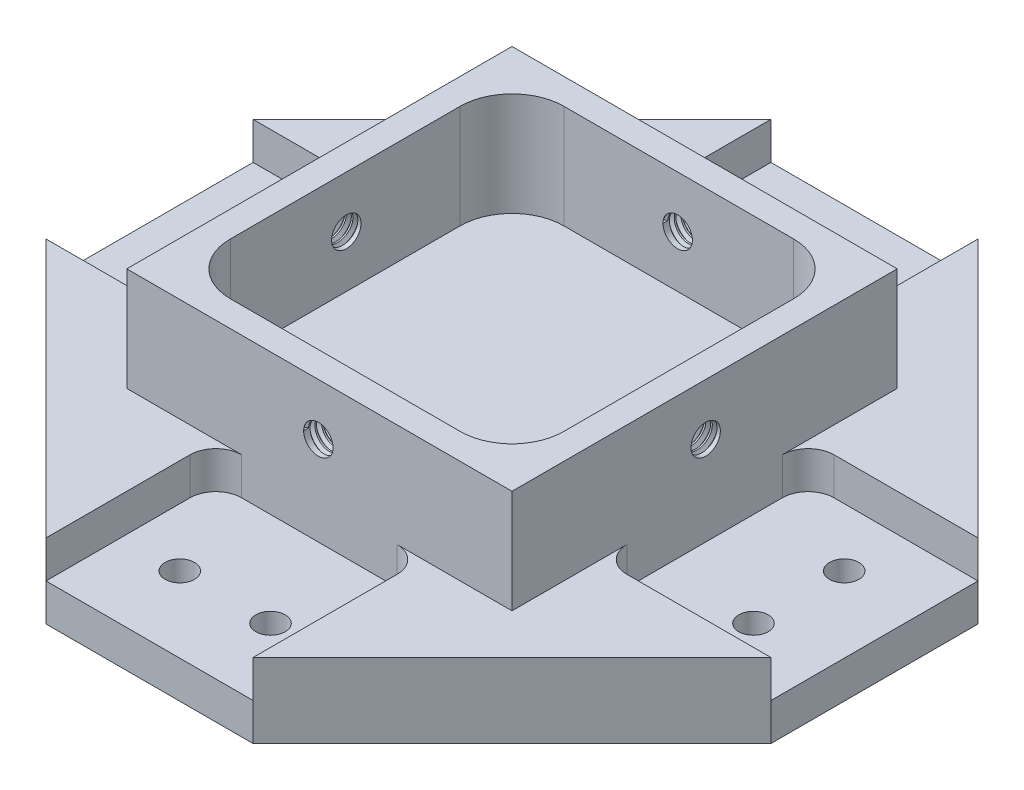
SolidWorks part; units mm, degrees
material "6061 Alloy"
ref_plane "Front Plane" through (0, 0, 0) normal (0, 0, 1) x (1, 0, 0)
ref_plane "Top Plane" through (0, 0, 0) normal (0, 1, 0) x (1, 0, 0)
ref_plane "Right Plane" through (0, 0, 0) normal (1, 0, 0) x (0, 0, -1)
sketch "Sketch1" plane through (0, 0, 0) normal (0, 1, 0) x (1, 0, 0)
  line L1 (0, 0) -> (88.9, 0)
  line L2 (0, 0) -> (0, 88.9)
  line L3 (0, 88.9) -> (88.9, 88.9)
  line L4 (88.9, 0) -> (88.9, 88.9)
  dimension "D1" = 88.9
  dimension "D2" = 88.9
extrude "Boss-Extrude1" add sketch "Sketch1" along normal blind 9.144
sketch "Sketch2" plane through (0, 9.144, 0) normal (0, 1, 0) x (1, 0, 0)
  line L0 (88.9, 88.9) -> (0, 88.9) construction
  line L1 (31.75, 88.9) -> (57.15, 88.9)
  line L2 (31.75, 88.9) -> (31.75, 67.31)
  line L3 (31.75, 67.31) -> (57.15, 67.31)
  line L4 (57.15, 88.9) -> (57.15, 67.31)
  line L5 (0, 88.9) -> (0, 0) construction
  line L6 (0, 57.15) -> (21.59, 57.15)
  line L7 (0, 57.15) -> (0, 31.75)
  line L8 (0, 31.75) -> (21.59, 31.75)
  line L9 (21.59, 57.15) -> (21.59, 31.75)
  line L10 (0, 0) -> (88.9, 0) construction
  line L11 (31.75, 0) -> (57.15, 0)
  line L12 (31.75, 0) -> (31.75, 21.59)
  line L13 (31.75, 21.59) -> (57.15, 21.59)
  line L14 (57.15, 0) -> (57.15, 21.59)
  line L15 (88.9, 0) -> (88.9, 88.9) construction
  line L16 (88.9, 57.15) -> (67.31, 57.15)
  line L17 (88.9, 57.15) -> (88.9, 31.75)
  line L18 (88.9, 31.75) -> (67.31, 31.75)
  line L19 (67.31, 57.15) -> (67.31, 31.75)
  dimension "D1" = 31.75
  dimension "D2" = 25.4
  dimension "D3" = 25.4
  dimension "D4" = 31.75
  dimension "D5" = 25.4
  dimension "D6" = 31.75
  dimension "D7" = 25.4
  dimension "D8" = 31.75
  dimension "D9" = 21.59
  dimension "D10" = 21.59
  dimension "D11" = 21.59
  dimension "D12" = 21.59
extrude "Cut-Extrude1" cut sketch "Sketch2" against normal blind 4.572
sketch "Sketch3" plane through (0, 9.144, 0) normal (0, 1, 0) x (1, 0, 0)
  line L0 (31.75, 88.9) -> (0, 88.9) construction
  line L1 (20.6375, 68.2625) -> (68.2625, 68.2625)
  line L2 (20.6375, 68.2625) -> (20.6375, 20.6375)
  line L3 (20.6375, 20.6375) -> (68.2625, 20.6375)
  line L4 (68.2625, 68.2625) -> (68.2625, 20.6375)
  line L5 (0, 31.75) -> (0, 0) construction
  line L6 (88.9, 31.75) -> (88.9, 57.15) construction
  line L7 (57.15, 88.9) -> (31.75, 88.9) construction
  line L8 (0, 57.15) -> (0, 31.75) construction
  line L9 (31.75, 0) -> (57.15, 0) construction
  circle A0 centre (28.194, 44.45) radius 2.4
  circle A1 centre (44.45, 60.706) radius 2.4
  circle A2 centre (60.706, 44.45) radius 2.4
  circle A3 centre (44.45, 28.194) radius 2.4
  dimension "D5" = 4.8
  dimension "D6" = 4.8
  dimension "D7" = 4.8
  dimension "D8" = 4.8
  dimension "D1" = 47.625
  dimension "D2" = 47.625
  dimension "D3" = 20.6375
  dimension "D4" = 20.6375
  dimension "D9" = 28.194
  dimension "D10" = 28.194
  dimension "D11" = 28.194
  dimension "D12" = 28.194
  dimension "D13" = 23.8125
  dimension "D14" = 23.8125
  dimension "D15" = 23.8125
  dimension "D16" = 23.8125
extrude "Cut-Extrude2" [suppressed] cut sketch "Sketch3" against normal through all contours A2 | A1 | A0 | A3
sketch "Sketch4" plane through (0, 4.572, 0) normal (0, 1, 0) x (1, 0, 0)
  line L0 (0, 57.15) -> (0, 31.75) construction
  line L1 (57.15, 88.9) -> (31.75, 88.9) construction
  line L2 (88.9, 31.75) -> (88.9, 57.15) construction
  line L3 (31.75, 0) -> (57.15, 0) construction
  line L4 (0, 31.75) -> (21.59, 31.75) construction
  line L5 (31.75, 21.59) -> (31.75, 0) construction
  line L6 (67.31, 31.75) -> (88.9, 31.75) construction
  line L7 (57.15, 67.31) -> (57.15, 88.9) construction
  circle A0 centre (79.629, 50.0126) radius 1.8034
  circle A1 centre (79.629, 38.8874) radius 1.8034
  circle A2 centre (50.0126, 79.629) radius 1.8034
  circle A3 centre (38.8874, 79.629) radius 1.8034
  circle A4 centre (9.271, 50.0126) radius 1.8034
  circle A5 centre (9.271, 38.8874) radius 1.8034
  circle A6 centre (38.8874, 9.271) radius 1.8034
  circle A7 centre (50.0126, 9.271) radius 1.8034
  dimension "D1" = 3.6068
  dimension "D2" = 3.6068
  dimension "D3" = 3.6068
  dimension "D4" = 3.6068
  dimension "D5" = 3.6068
  dimension "D6" = 3.6068
  dimension "D7" = 3.6068
  dimension "D8" = 3.6068
  dimension "D9" = 9.271
  dimension "D10" = 9.271
  dimension "D11" = 9.271
  dimension "D12" = 9.271
  dimension "D13" = 9.271
  dimension "D14" = 9.271
  dimension ".313" = 9.271
  dimension "D16" = 9.271
  dimension "D17" = 11.1252
  dimension "D18" = 7.1374
  dimension "D19" = 7.1374
  dimension "D20" = 11.1252
  dimension "D21" = 7.1374
  dimension "D22" = 11.1252
  dimension "D23" = 7.1374
  dimension "D24" = 11.1252
extrude "Cut-Extrude3" cut sketch "Sketch4" against normal through all
sketch "Sketch5" plane through (0, 9.144, 0) normal (0, 1, 0) x (1, 0, 0)
  line L0 (88.9, 88.9) -> (57.15, 88.9) construction
  line L1 (88.9, 31.75) -> (88.9, 57.15) construction
  circle A0 centre (44.45, 44.45) radius 6.35
  dimension "D1" = 12.7
  dimension "D2" = 44.45
  dimension "D3" = 44.45
extrude "Cut-Extrude4" [suppressed] cut sketch "Sketch5" against normal through all
sketch "Sketch6" plane through (0, 9.144, 0) normal (0, 1, 0) x (1, 0, 0)
  line L0 (88.9, 31.75) -> (57.15, 0)
  line L1 (57.15, 0) -> (88.9, 0)
  line L2 (88.9, 0) -> (88.9, 31.75)
extrude "Cut-Extrude5" cut sketch "Sketch6" against normal through all
sketch "Sketch7" plane through (0, 9.144, 0) normal (0, 1, 0) x (1, 0, 0)
  line L0 (0, 88.9) -> (0, 57.15) construction
  line L1 (20.828, 68.072) -> (68.072, 68.072)
  line L2 (20.828, 68.072) -> (20.828, 20.828)
  line L3 (20.828, 20.828) -> (68.072, 20.828)
  line L4 (68.072, 68.072) -> (68.072, 20.828)
  line L5 (0, 0) -> (31.75, 0) construction
  line L7 (24.003, 24.003) -> (64.897, 24.003)
  line L8 (24.003, 24.003) -> (24.003, 64.897)
  line L9 (24.003, 64.897) -> (64.897, 64.897)
  line L10 (64.897, 24.003) -> (64.897, 64.897)
  dimension "D1" = 47.244
  dimension "D2" = 47.244
  dimension "D3" = 20.828
  dimension "D4" = 20.828
  dimension "D5" = 3.175
  dimension "D6" = 3.175
  dimension "D7" = 3.175
  dimension "D8" = 3.175
extrude "Boss-Extrude2" add sketch "Sketch7" along normal blind 12.7 and the other way up to next (4.572 mm away)
fillet "Fillet9" radius 6.35 1 edges at (64.897, 15.494, -24.003)
fillet "Fillet10" radius 6.35 1 edges at (24.003, 15.494, -24.003)
fillet "Fillet11" radius 6.35 1 edges at (64.897, 15.494, -64.897)
fillet "Fillet12" radius 6.35 1 edges at (24.003, 15.494, -64.897)
fillet "Fillet15" radius 3.175 1 edges at (20.828, 6.858, -57.15)
fillet "Fillet16" radius 3.175 1 edges at (31.75, 6.858, -20.828)
fillet "Fillet17" radius 3.175 1 edges at (57.15, 6.858, -20.828)
fillet "Fillet18" radius 3.175 1 edges at (68.072, 6.858, -57.15)
fillet "Fillet19" radius 3.175 1 edges at (68.072, 6.858, -31.75)
fillet "Fillet20" radius 3.175 1 edges at (31.75, 6.858, -68.072)
fillet "Fillet21" radius 3.175 1 edges at (57.15, 6.858, -68.072)
fillet "Fillet22" radius 3.175 1 edges at (20.828, 6.858, -31.75)
sketch "Sketch9" plane through (0, 0, -68.072) normal (0, 0, -1) x (-1, 0, 0)
  line L0 (-68.072, 21.844) -> (-68.072, 9.144) construction
  line L1 (-68.072, 21.844) -> (-20.828, 21.844) construction
  circle A0 centre (-44.323, 15.494) radius 1.8034
  dimension "D1" = 3.6068
  dimension "D2" = 23.749
  dimension "D3" = 6.35
extrude "Cut-Extrude6" cut sketch "Sketch9" against normal through all
sketch "Sketch10" plane through (68.072, 0, 0) normal (1, 0, 0) x (0, 0, -1)
  line L0 (20.828, 21.844) -> (68.072, 21.844) construction
  line L1 (20.828, 21.844) -> (20.828, 9.144) construction
  circle A0 centre (44.577, 15.494) radius 1.8034
  dimension "D1" = 3.6068
  dimension "D2" = 6.35
  dimension "D3" = 23.749
extrude "Cut-Extrude7" cut sketch "Sketch10" against normal through all
sketch "Sketch12" plane through (0, 9.144, 0) normal (0, 1, 0) x (1, 0, 0)
  line L0 (0, 31.75) -> (31.75, 0)
  line L1 (31.75, 0) -> (0, 0)
  line L2 (0, 0) -> (0, 31.75)
  line L3 (57.15, 88.9) -> (88.9, 57.15)
  line L4 (88.9, 57.15) -> (88.9, 88.9)
  line L5 (88.9, 88.9) -> (57.15, 88.9)
  line L6 (0, 57.15) -> (31.75, 88.9)
  line L7 (31.75, 88.9) -> (0, 88.9)
  line L8 (0, 88.9) -> (0, 57.15)
sketch "Sketch14" plane through (0, 0, 0) normal (0, -1, 0) x (1, 0, 0)
  line L0 (60.2924, -60.2924) -> (28.8616, -28.8616) construction
  line L6 (24.003, -58.547) -> (24.003, -30.353) construction
  line L7 (30.353, -24.003) -> (58.547, -24.003) construction
  circle A0 centre (28.8616, -28.8616) radius 2.5797
  circle A1 centre (60.2924, -60.2924) radius 2.5797
  point P0 (44.577, -44.577)
  dimension "D1" = 44.45
  dimension "D2" = 5.1594
  dimension "D3" = 5.1594
  dimension "D4" = 20.574
  dimension "D5" = 20.574
extrude "Cut-Extrude9" cut sketch "Sketch14" against normal through all
extrude "Cut-Extrude10" cut sketch "Sketch12" against normal through all
thread "Thread1" pitch 0.7937 method cut profile "Thread Profile1" start angle 0, offset 0, length 0, pitch 0.7937, diameter 3.6068
ref_plane "Plane1" through (42.5196, 15.494, -20.828) normal (0, -1, 0) x (-1, 0, 0)
sketch "Thread Profile1" plane through (42.5196, 15.494, -20.828) normal (0, -1, 0) x (-1, 0, 0)
  line L0 (0, 0) -> (0, 0.7937) construction
  line L1 (0, 0) -> (0.4296, 0.248)
  line L2 (0.4296, 0.248) -> (0.4296, 0.3473)
  line L3 (0.4296, 0.3473) -> (0, 0.5953)
  line L4 (0.4296, 0.2977) -> (0, 0.2977) construction
  line L11 (0, 0) -> (0, 0.5953)
  point P2 (0, 0)
  dimension "Pitch" = 0.7937
  dimension "Profile_Angle" = 60
  dimension "Profile_Land" = 0.0992
  dimension "Profile_Height" = 0.4296
thread "Thread2" pitch 0.7937 method cut profile "Thread Profile2" start angle 0, offset 0, length 0, pitch 0.7937, diameter 3.6068
ref_plane "Plane2" through (68.072, 15.494, -42.7736) normal (0, -1, 0) x (0, 0, 1)
sketch "Thread Profile2" plane through (68.072, 15.494, -42.7736) normal (0, -1, 0) x (0, 0, 1)
  line L0 (0, 0) -> (0, 0.7937) construction
  line L1 (0, 0) -> (0.4296, 0.248)
  line L2 (0.4296, 0.248) -> (0.4296, 0.3473)
  line L3 (0.4296, 0.3473) -> (0, 0.5953)
  line L4 (0.4296, 0.2977) -> (0, 0.2977) construction
  line L11 (0, 0) -> (0, 0.5953)
  point P2 (0, 0)
  dimension "Pitch" = 0.7937
  dimension "Profile_Angle" = 60
  dimension "Profile_Land" = 0.0992
  dimension "Profile_Height" = 0.4296
thread "Thread3" pitch 0.7937 method cut profile "Thread Profile3" start angle 0, offset 0, length 0, pitch 0.7937, diameter 3.6068
ref_plane "Plane3" through (42.5196, 15.494, -64.897) normal (0, -1, 0) x (-1, 0, 0)
sketch "Thread Profile3" plane through (42.5196, 15.494, -64.897) normal (0, -1, 0) x (-1, 0, 0)
  line L0 (0, 0) -> (0, 0.7937) construction
  line L1 (0, 0) -> (0.4296, 0.248)
  line L2 (0.4296, 0.248) -> (0.4296, 0.3473)
  line L3 (0.4296, 0.3473) -> (0, 0.5953)
  line L4 (0.4296, 0.2977) -> (0, 0.2977) construction
  line L11 (0, 0) -> (0, 0.5953)
  point P2 (0, 0)
  dimension "Pitch" = 0.7937
  dimension "Profile_Angle" = 60
  dimension "Profile_Land" = 0.0992
  dimension "Profile_Height" = 0.4296
thread "Thread4" pitch 0.7937 method cut profile "Thread Profile4" start angle 0, offset 0, length 0, pitch 0.7937, diameter 3.6068
ref_plane "Plane4" through (24.003, 15.494, -42.7736) normal (0, -1, 0) x (0, 0, 1)
sketch "Thread Profile4" plane through (24.003, 15.494, -42.7736) normal (0, -1, 0) x (0, 0, 1)
  line L0 (0, 0) -> (0, 0.7937) construction
  line L1 (0, 0) -> (0.4296, 0.248)
  line L2 (0.4296, 0.248) -> (0.4296, 0.3473)
  line L3 (0.4296, 0.3473) -> (0, 0.5953)
  line L4 (0.4296, 0.2977) -> (0, 0.2977) construction
  line L11 (0, 0) -> (0, 0.5953)
  point P2 (0, 0)
  dimension "Pitch" = 0.7937
  dimension "Profile_Angle" = 60
  dimension "Profile_Land" = 0.0992
  dimension "Profile_Height" = 0.4296
equation "\"hinge_hole\"= 0.142in"
equation "\"D1@Sketch4\"=\"hinge_hole\""
equation "\"D2@Sketch4\"=\"hinge_hole\""
equation "\"D3@Sketch4\"=\"hinge_hole\""
equation "\"D4@Sketch4\"=\"hinge_hole\""
equation "\"D5@Sketch4\"=\"hinge_hole\""
equation "\"D6@Sketch4\"=\"hinge_hole\""
equation "\"D7@Sketch4\"=\"hinge_hole\""
equation "\"D8@Sketch4\"=\"hinge_hole\""
equation "\"hinge_hole_dist\"= 0.297 + 0.25"
equation "\"hinge_hole_sep\"=0.438"
equation "\"hinge_hole_from_wall\"= ( 1 - \"hinge_hole_sep\" ) / 2"
equation "\"D17@Sketch4\"=\"hinge_hole_sep\""
equation "\"D18@Sketch4\"=\"hinge_hole_from_wall\""
equation "\"D19@Sketch4\"=\"hinge_hole_from_wall\""
equation "\"D20@Sketch4\"=\"hinge_hole_sep\""
equation "\"D21@Sketch4\"=\"hinge_hole_from_wall\""
equation "\"D22@Sketch4\"=\"hinge_hole_sep\""
equation "\"D23@Sketch4\"=\"hinge_hole_from_wall\""
equation "\"D24@Sketch4\"=\"hinge_hole_sep\""
equation "\"D9@Sketch2\"=\"hinge_hole_dist\" + (0.6-0.297)"
equation "\"D12@Sketch2\"=\"hinge_hole_dist\" + (0.6-0.297)"
equation "\"D11@Sketch2\"=\"hinge_hole_dist\" + (0.6-0.297)"
equation "\"D10@Sketch2\"=\"hinge_hole_dist\" + (0.6-0.297)"
